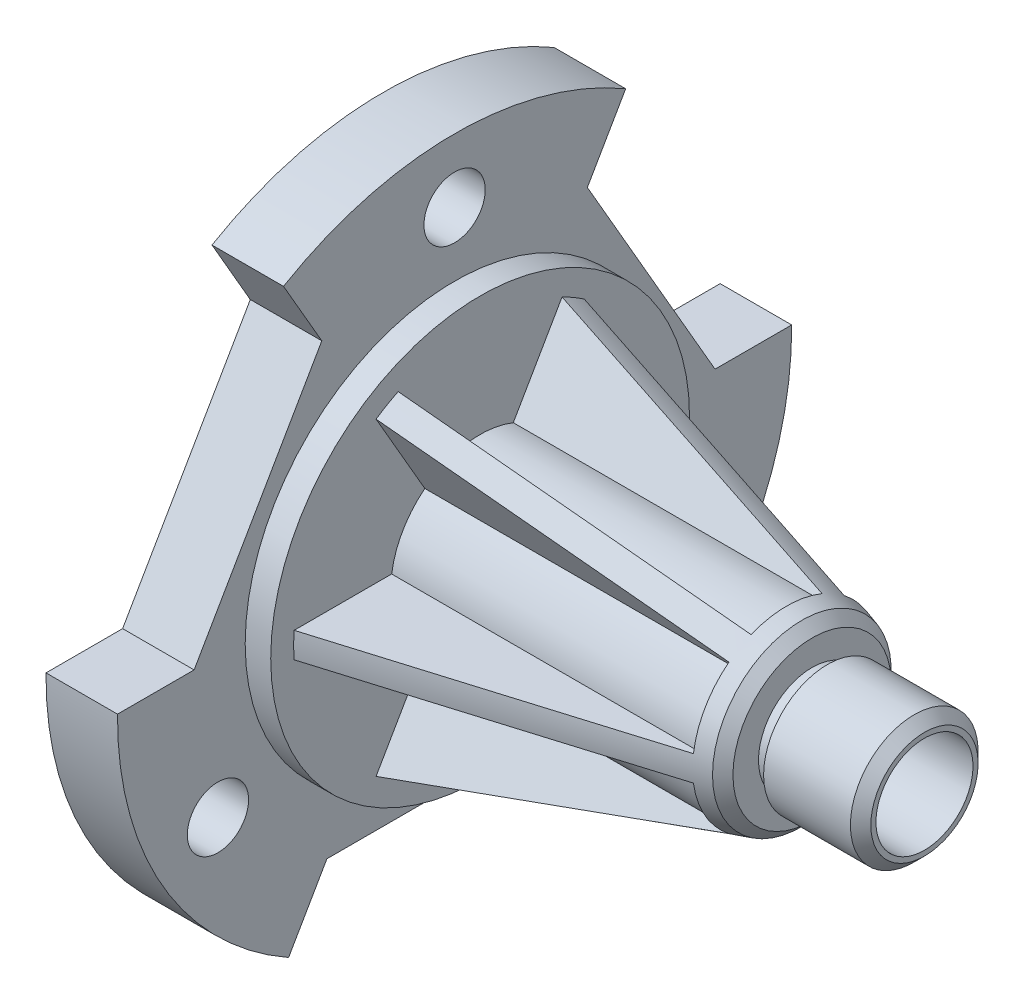
SolidWorks part; units mm, degrees
ref_plane "Front Plane" through (0, 0, 0) normal (0, 0, 1) x (1, 0, 0)
ref_plane "Top Plane" through (0, 0, 0) normal (0, 1, 0) x (1, 0, 0)
ref_plane "Right Plane" through (0, 0, 0) normal (1, 0, 0) x (0, 0, -1)
sketch "Sketch1" plane through (0, 0, 0) normal (0, 0, 1) x (1, 0, 0)
  line L0 (0, 0) -> (0, 66)
  line L1 (0, 66) -> (14, 66)
  line L2 (14, 66) -> (14, 41)
  line L3 (14, 41) -> (19, 41)
  line L4 (19, 41) -> (19, 17.5)
  line L5 (19, 17.5) -> (84, 17.5)
  line L6 (84, 17.5) -> (84, 12.5)
  line L9 (84, 12.5) -> (106, 12.5)
  line L10 (106, 12.5) -> (106, 0)
  line L11 (106, 0) -> (0, 0)
  line L12 (0, 0) -> (149.5223, 0) construction
  point P9 (0, 0)
  dimension "D2" = 14
  dimension "D3" = 106
  dimension "D5" = 12.5
  dimension "D6" = 22
  dimension "D7" = 17.5
  dimension "D8" = 66
  dimension "D9" = 41
  dimension "D10" = 5
revolve "Revolve3" add sketch "Sketch1" angle 360 about L12
sketch "Sketch2" plane through (0, 0, 0) normal (0, 0, 1) x (1, 0, 0)
  line L0 (84, -17.5) -> (84, 17.5) construction
  line L1 (84, 12.5) -> (87, 12.5)
  line L2 (84, 12.5) -> (84, 10.5)
  line L3 (84, 10.5) -> (87, 10.5)
  line L4 (87, 12.5) -> (87, 10.5)
  line L5 (84, -12.5) -> (84, 12.5) construction
  line L6 (106, 12.5) -> (84, 12.5) construction
  line L7 (0, 0) -> (114.0295, 0) construction
  dimension "D1" = 2
  dimension "D2" = 3
revolve "Cut-Revolve1" cut sketch "Sketch2" angle 360 about L7
sketch "Sketch3" plane through (0, 0, 0) normal (0, 1, 0) x (1, 0, 0)
  line L0 (19, 36.5) -> (82, 17.5)
  line L1 (19, -41) -> (19, 41) construction
  line L2 (84, 17.5) -> (19, 17.5) construction
  line L3 (82, 17.5) -> (19, 17.5)
  line L4 (19, 17.5) -> (19, 36.5)
  line L5 (0, 0) -> (158.4698, 0) construction
  dimension "D1" = 19
  dimension "D2" = 2
revolve "Revolve5" add sketch "Sketch3" angle 360 about L5
chamfer "Chamfer1" distance 2 angle 45 2 edges at (106, 0, 12.5) (84, 0, 17.5)
sketch "Sketch4" plane through (14, 0, 0) normal (1, 0, 0) x (0, 0, -1)
  line L0 (0, 0) -> (0, -72.6795) construction
  line L1 (-32.5, -57.4435) -> (-25, -44.4531)
  line L2 (-25, -44.4531) -> (25, -44.4531)
  line L3 (25, -44.4531) -> (32.5, -57.4435)
  circle A0 centre (0, 0) radius 66 construction
  arc A1 (-32.5, -57.4435) -> (32.5, -57.4435) centre (0, 0) ccw
  dimension "D1" = 60
  dimension "D2" = 50
  dimension "D3" = 65
extrude "Cut-Extrude1" cut sketch "Sketch4" against normal through all
pattern_circular "CirPattern1" count 3 over 360 about axis through (0, 0, 0) along (1, 0, 0) of "Cut-Extrude1"
hole_wizard "Hole1" positions "Sketch5" profile "Sketch6" legacy end condition up to next
sketch "Sketch5" plane through (14, 0, 0) normal (1, 0, 0) x (0, 0, -1)
  point P0 (0, 53.5)
  dimension "D1" = 53.5
sketch "Sketch6" plane through (14, 53.5, 0) normal (0, 1, 0) x (0, 0, -1)
  line L0 (0, 0) -> (0, 14)
  line L1 (0, 14) -> (6, 14)
  line L2 (6, 14) -> (6, 0)
  line L3 (6, 0) -> (0, 0)
  line L4 (0, 110) -> (0, -10) construction
  dimension "Diameter" = 12
  dimension "Depth" = 14
pattern_circular "CirPattern2" count 3 over 360 about axis through (0, 0, 0) along (1, 0, 0) of "Hole1"
sketch "Sketch7" plane through (0, 0, 0) normal (-1, 0, 0) x (0, 0, 1)
  line L0 (0, 0) -> (76.0296, 0) construction
  line L1 (17.3205, 2.5) -> (40.9237, 2.5)
  line L2 (17.3205, -2.5) -> (40.9237, -2.5)
  line L3 (6.4952, -16.25) -> (18.2968, -36.691)
  line L4 (10.8253, -13.75) -> (22.6269, -34.191)
  line L5 (-10.8253, -13.75) -> (-22.6269, -34.191)
  line L6 (-6.4952, -16.25) -> (-18.2968, -36.691)
  line L7 (-17.3205, 2.5) -> (-40.9237, 2.5)
  line L8 (-17.3205, -2.5) -> (-40.9237, -2.5)
  line L9 (-6.4952, 16.25) -> (-18.2968, 36.691)
  line L10 (-10.8253, 13.75) -> (-22.6269, 34.191)
  line L11 (10.8253, 13.75) -> (22.6269, 34.191)
  line L12 (6.4952, 16.25) -> (18.2968, 36.691)
  arc A0 (-22.6269, 34.191) -> (-40.9237, 2.5) centre (0, 0) ccw
  arc A1 (-10.8253, 13.75) -> (-17.3205, 2.5) centre (0, 0) ccw
  arc A2 (-17.3205, -2.5) -> (-10.8253, -13.75) centre (0, 0) ccw
  arc A3 (-40.9237, -2.5) -> (-22.6269, -34.191) centre (0, 0) ccw
  arc A4 (-18.2968, -36.691) -> (18.2968, -36.691) centre (0, 0) ccw
  arc A5 (-6.4952, -16.25) -> (6.4952, -16.25) centre (0, 0) ccw
  arc A6 (10.8253, -13.75) -> (17.3205, -2.5) centre (0, 0) ccw
  arc A7 (22.6269, -34.191) -> (40.9237, -2.5) centre (0, 0) ccw
  arc A8 (40.9237, 2.5) -> (22.6269, 34.191) centre (0, 0) ccw
  arc A9 (17.3205, 2.5) -> (10.8253, 13.75) centre (0, 0) ccw
  arc A10 (6.4952, 16.25) -> (-6.4952, 16.25) centre (0, 0) ccw
  arc A11 (18.2968, 36.691) -> (-18.2968, 36.691) centre (0, 0) ccw
  point P8 (0, 0)
  point P31 (0, 0)
  dimension "D1" = 82
  dimension "D2" = 35
  dimension "D3" = 5
  dimension "D4" = 6
extrude "Cut-Extrude2" cut sketch "Sketch7" against normal blind 79
sketch "Sketch9" plane through (0, 0, 0) normal (-1, 0, 0) x (0, 0, 1)
  circle A0 centre (0, 0) radius 41
  arc A1 (-18.2968, -36.691) -> (18.2968, -36.691) centre (0, 0) ccw construction
extrude "Boss-Extrude2" add sketch "Sketch9" against normal blind 19
hole_wizard "Hole3" positions "Sketch13" profile "Sketch14" legacy end condition up to next
sketch "Sketch13" plane through (0, 0, 0) normal (-1, 0, 0) x (0, 0, 1)
  point P0 (0, 0)
  point P4 (0, 0)
sketch "Sketch14" plane through (0, 0, 0) normal (0, 1, 0) x (0, 0, 1)
  line L0 (0, 0) -> (0, 106)
  line L1 (0, 106) -> (9.5, 106)
  line L2 (9.5, 106) -> (9.5, 4)
  line L3 (9.5, 4) -> (22, 4)
  line L4 (22, 4) -> (22, 0)
  line L5 (22, 0) -> (0, 0)
  line L6 (0, 110) -> (0, -10) construction
  dimension "Diameter" = 19
  dimension "Depth" = 106
  dimension "C-Bore Diameter" = 44
  dimension "C-Bore Depth" = 4
